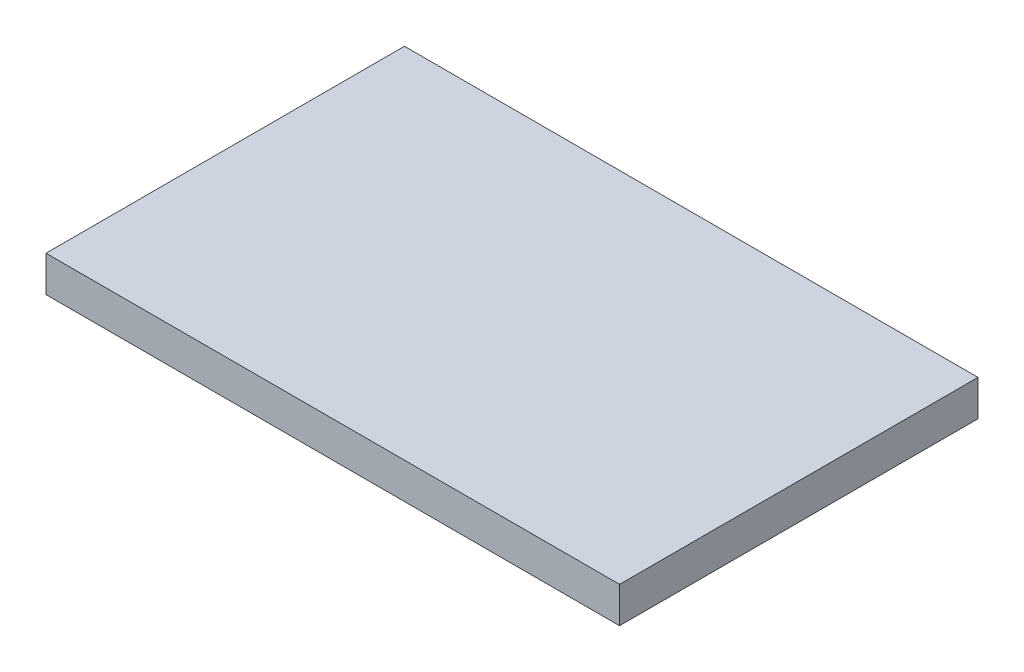
SolidWorks part; units mm, degrees
ref_plane "Front Plane" through (0, 0, 0) normal (0, 0, 1) x (1, 0, 0)
ref_plane "Top Plane" through (0, 0, 0) normal (0, 1, 0) x (1, 0, 0)
ref_plane "Right Plane" through (0, 0, 0) normal (1, 0, 0) x (0, 0, -1)
sketch "Sketch1" plane through (0, 0, 0) normal (0, 1, 0) x (1, 0, 0)
  line L1 (-48, -30) -> (48, -30)
  line L2 (-48, -30) -> (-48, 30)
  line L3 (-48, 30) -> (48, 30)
  line L4 (48, -30) -> (48, 30)
  line L5 (-48, -30) -> (48, 30) construction
  line L6 (-48, 30) -> (48, -30) construction
  point P0 (0, 0)
  dimension "D1" = 96
  dimension "D2" = 60
extrude "Boss-Extrude1" add sketch "Sketch1" along normal blind 6
